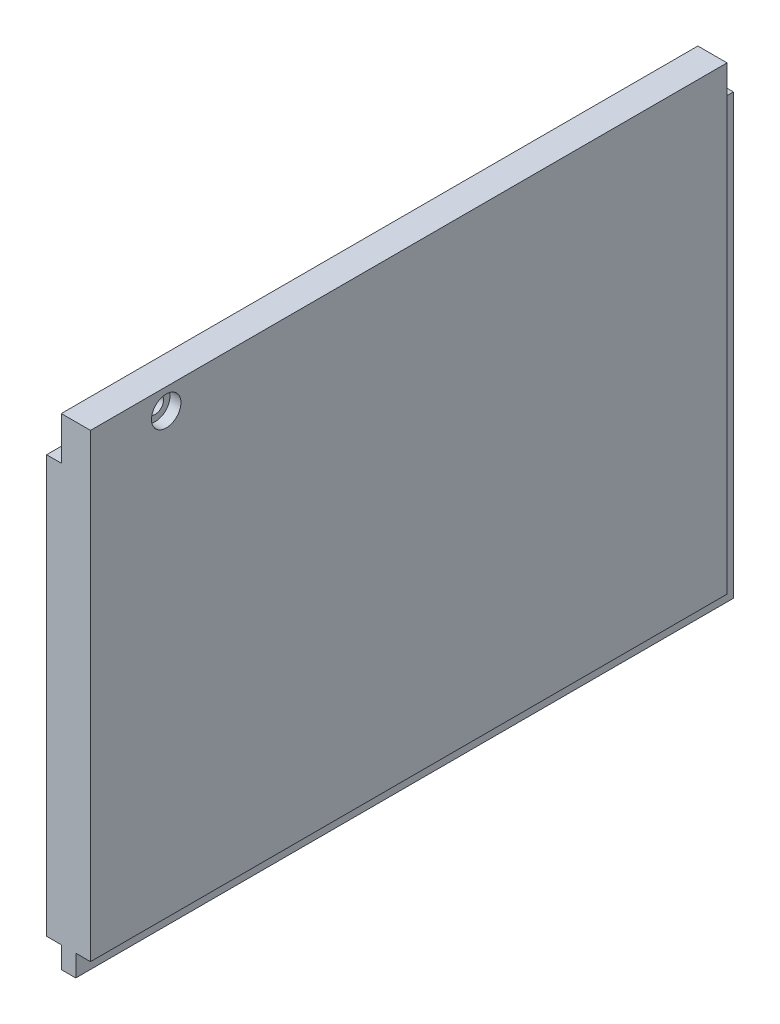
SolidWorks part; units mm, degrees
ref_plane "Front Plane" through (0, 0, 0) normal (1, 0, 0) x (0, 1, 0)
ref_plane "Top Plane" through (0, 0, 0) normal (0, 0, 1) x (0, 1, 0)
ref_plane "Right Plane" through (0, 0, 0) normal (0, 1, 0) x (-1, 0, 0)
sketch "Sketch1" plane through (0, 0, 0) normal (1, 0, 0) x (0, 1, 0)
  line L1 (0, 0) -> (95, 0)
  line L2 (0, 0) -> (0, 145)
  line L3 (0, 145) -> (95, 145)
  line L4 (95, 0) -> (95, 145)
  dimension "D1" = 95
  dimension "D2" = 145
extrude "Boss-Extrude1" add sketch "Sketch1" against normal blind 10
sketch "Sketch2" plane through (0, 0, 0) normal (0, -1, 0) x (1, 0, 0)
  line L0 (-10, 0) -> (0, 0) construction
  line L1 (-10, 0) -> (-6.65, 0) construction
  line L2 (-10, 0) -> (-10, -4.8) construction
  line L3 (-10, -4.8) -> (-6.65, -4.8) construction
  line L4 (-6.65, 0) -> (-6.65, -4.8) construction
  line L5 (0, 0) -> (-3.35, 0) construction
  line L6 (0, 0) -> (0, -4.8) construction
  line L7 (0, -4.8) -> (-3.35, -4.8) construction
  line L8 (-3.35, 0) -> (-3.35, -4.8) construction
  line L9 (-6.65, -4.8) -> (-3.35, -4.8)
  line L10 (-6.65, -4.8) -> (-6.65, 0)
  line L11 (-6.65, 0) -> (-3.35, 0)
  line L12 (-3.35, -4.8) -> (-3.35, 0)
  dimension "D1" = 3.35
  dimension "D2" = 3.35
  dimension "D3" = 4.8
extrude "Boss-Extrude2" add sketch "Sketch2" against normal up to surface (95 mm away) up to face at (-5, 95, 72.5)
sketch "Sketch3" plane through (0, 0, 0) normal (0, -1, 0) x (1, 0, 0)
  line L0 (-10, 145) -> (-10, 0) construction
  line L1 (-10, 145) -> (-6.65, 145) construction
  line L2 (-10, 145) -> (-10, -4.8) construction
  line L3 (-10, -4.8) -> (-6.65, -4.8) construction
  line L4 (-6.65, 145) -> (-6.65, -4.8) construction
  line L5 (-3.35, -4.8) -> (0, -4.8) construction
  line L6 (-3.35, -4.8) -> (-3.35, 145) construction
  line L7 (-3.35, 145) -> (0, 145) construction
  line L8 (0, -4.8) -> (0, 145) construction
  line L9 (-3.35, 145) -> (-6.65, 145)
  line L10 (-3.35, 145) -> (-3.35, -4.8)
  line L11 (-3.35, -4.8) -> (-6.65, -4.8)
  line L12 (-6.65, 145) -> (-6.65, -4.8)
  line L13 (-10, 145) -> (0, 145) construction
  line L14 (-3.35, -4.8) -> (-3.35, 0) construction
  line L15 (-6.65, -4.8) -> (-3.35, -4.8) construction
  dimension "D1" = 3.3
extrude "Boss-Extrude3" add sketch "Sketch3" along normal blind 4.9
sketch "Sketch4" plane through (0, 95, 0) normal (0, 1, 0) x (-1, 0, 0)
  line L1 (0, 145) -> (6.65, 145)
  line L2 (0, 145) -> (0, 0)
  line L3 (0, 0) -> (6.65, 0)
  line L4 (6.65, 145) -> (6.65, 0)
  line L5 (10, 145) -> (0, 145) construction
  line L6 (6.65, 0) -> (10, 0)
  line L7 (6.65, 0) -> (6.65, 145)
  line L8 (6.65, 145) -> (10, 145)
  line L9 (10, 0) -> (10, 145)
  line L10 (0, 0) -> (0, 145) construction
  line M22 (0, 145) -> (0, 0)
  line M23 (0, 0) -> (3.35, 0)
  line M29 (10, 145) -> (0, 145)
  dimension "D1" = 3.35
  dimension "D2" = 6.65
extrude "Boss-Extrude4" add sketch "Sketch4" along normal blind 10 contours L4 L3 M29 M22 M23 region at (-3.325, 95, 72.5)
sketch "Sketch5" plane through (0, 0, 0) normal (1, 0, 0) x (0, 1, 0)
  line L1 (105, 145) -> (100, 145) construction
  line L2 (105, 145) -> (105, 127.75) construction
  line L3 (105, 127.75) -> (100, 127.75) construction
  line L4 (100, 145) -> (100, 127.75) construction
  circle A0 centre (100, 127.75) radius 1.9
  dimension "D3" = 3.8
  dimension "D1" = 17.25
  dimension "D2" = 5
extrude "Cut-Extrude1" cut sketch "Sketch5" against normal up to next
sketch "Sketch6" plane through (0, 0, 0) normal (1, 0, 0) x (0, 1, 0)
  circle A0 centre (100, 127.75) radius 3.35
  dimension "D1" = 6.7
extrude "Cut-Extrude2" cut sketch "Sketch6" against normal blind 2.5
sketch "Sketch7" plane through (0, 0, 0) normal (1, 0, 0) x (0, 1, 0)
  line L0 (0, 0) -> (105, 0) construction
  line L1 (105, 145) -> (104.8, 145)
  line L2 (105, 145) -> (105, 0)
  line L3 (105, 0) -> (104.8, 0)
  line L4 (104.8, 145) -> (104.8, 0)
  dimension "D1" = 0.2
extrude "Cut-Extrude3" cut sketch "Sketch7" against normal up to next
sketch "Sketch8" plane through (-10, 0, 0) normal (-1, 0, 0) x (0, -1, 0)
  line L0 (-90, 140) -> (-90, 5)
  line L1 (-95, 145) -> (0, 145)
  line L2 (-95, 145) -> (-95, 0)
  line L3 (-95, 0) -> (0, 0)
  line L4 (0, 145) -> (0, 0)
  line L5 (-90, 5) -> (-5, 5)
  line L6 (-5, 140) -> (-5, 5)
  line L7 (-90, 140) -> (-5, 140)
  dimension "D1" = 5
extrude "Cut-Extrude4" cut sketch "Sketch8" against normal blind 5 contours L7 L0 L5 L6 region at (-10, 47.5, 72.5)
chamfer "Chamfer1" distance 5 distance2 2.5 4 edges at (-10, 5, 72.5) (-10, 47.5, 5) (-10, 90, 72.5) (-10, 47.5, 140) first distance on face at (-7.5, 5, 72.5) first distance on face at (-7.5, 47.5, 5) first distance on face at (-7.5, 90, 72.5) first distance on face at (-7.5, 47.5, 140)
equation "\"whitekey_cutout_length\"= 101.5"
equation "\"whitekey_spacing\"=1.25"
equation "\"key_mount_recess_length\"=50"
equation "\"key_mount_recess_height\"=12.5"
equation "\"key_mount_recess_depth\"=1.5"
equation "\"wall_thickness\"=10"
equation "\"guide_brace_height\"=20"
equation "\"guide_brace_thickness\"=2"
equation "\"dowel_recess_depth\"=10"
equation "\"dowel_recess_offset\"=3.25"
equation "\"dowel_insert_tolerance\"=0.1"
equation "\"base_mount_height\"=40"
equation "\"base_rear_length\"=80"
equation "\"base_front_length\"=111.5"
equation "\"screw_hole_wall_offset\"=7.25"
equation "\"screw_hole_edge_inset\"=\"dowel_recess_depth\"/2"
equation "\"screw_hole_diameter\"=3.8"
equation "\"screw_head_hole_diameter\"=6.7"
equation "\"screw_nut_hole_side_len\"=3.5"
equation "\"screw_nut_recess_offset\"=0.35"
equation "\"screw_head_and_nut_recess_depth\"=2.5"
equation "\"screw_shaft_diameter\"=3.5"
equation "\"switch_board_width\"=30"
equation "\"switch_board_thickness\"=1.6"
equation "\"switch_board_wall_offset\"=11.5"
equation "\"heatset_insert_hole_diameter\"=4.8"
equation "\"heatset_insert_hole_depth\"=3.8"
equation "\"front_rear_panel_width\"=23.75"
equation "\"front_panel_height\"=24"
equation "\"front_rear_panel_recess_depth\"=5"
equation "\"rod_diameter\"=5"
equation "\"rod_head_diameter\"=8"
equation "\"rod_length_adj\"=0.5"
equation "\"rod_insert_length\"=2.8"
equation "\"switch_black_key_mount_height\"=8"
equation "\"switch_white_key_mount_height\"=3"
equation "\"side_panel_depth\"=35"
equation "\"interface_panel_height\"=135"
equation "\"interface_panel_roof_length\"=50"
equation "\"D2@Sketch1\"=\"interface_panel_height\"+\"wall_thickness\""
equation "\"D1@Sketch1\"=\"front_rear_panel_width\"*4"
equation "\"D1@Boss-Extrude1\"=\"wall_thickness\""
equation "\"D3@Sketch2\"=\"front_rear_panel_recess_depth\"-\"dowel_insert_tolerance\"*2"
equation "\"D2@Sketch2\"=\"dowel_recess_offset\"+\"dowel_insert_tolerance\""
equation "\"D1@Sketch2\"=\"dowel_recess_offset\"+\"dowel_insert_tolerance\""
equation "\"D1@Boss-Extrude3\"=\"front_rear_panel_recess_depth\"-\"dowel_insert_tolerance\""
equation "\"D1@Sketch4\"=\"dowel_recess_offset\"+\"dowel_insert_tolerance\""
equation "\"D1@Boss-Extrude4\"=\"dowel_recess_depth\""
equation "\"D1@Sketch5\"=\"wall_thickness\"+\"screw_hole_wall_offset\""
equation "\"D2@Sketch5\"=\"screw_hole_edge_inset\""
equation "\"D3@Sketch5\"=\"screw_hole_diameter\""
equation "\"D1@Sketch6\"=\"screw_head_hole_diameter\""
equation "\"D1@Cut-Extrude2\"=\"screw_head_and_nut_recess_depth\""
equation "\"D1@Sketch7\"=\"dowel_insert_tolerance\"*2"
equation "\"D1@Cut-Extrude4\"=\"wall_thickness\"/2"
